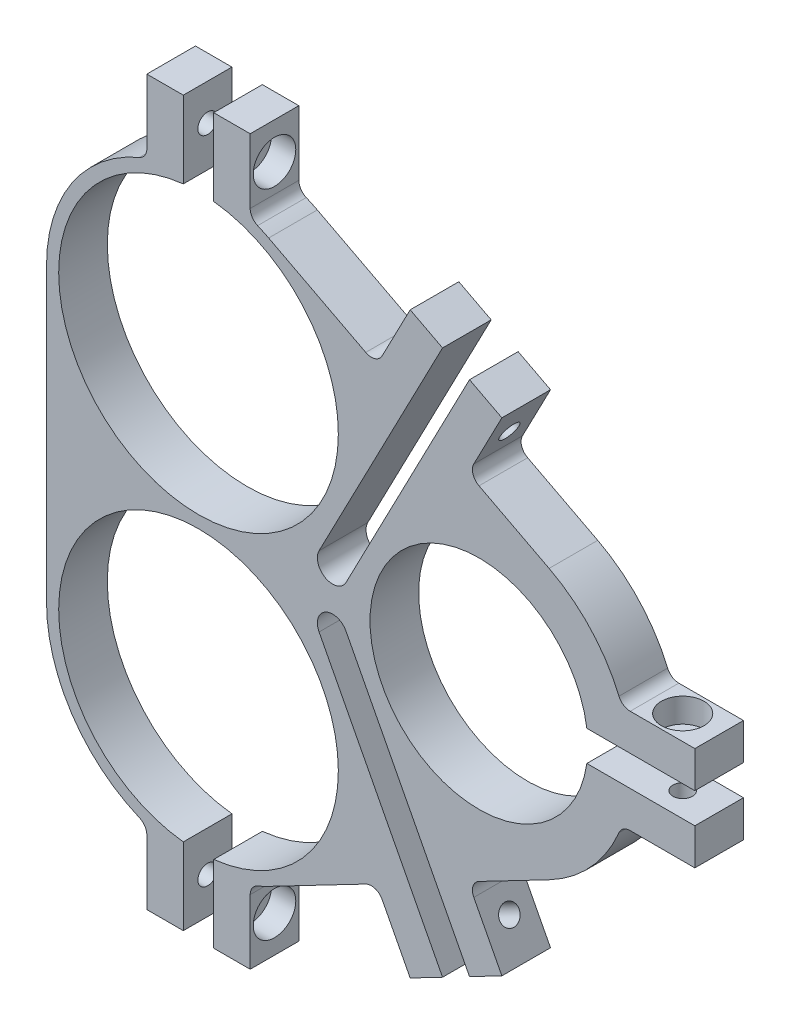
SolidWorks part; units mm, degrees
ref_plane "Front Plane" through (0, 0, 0) normal (0, 0, 1) x (1, 0, 0)
ref_plane "Top Plane" through (0, 0, 0) normal (0, 1, 0) x (1, 0, 0)
ref_plane "Right Plane" through (0, 0, 0) normal (1, 0, 0) x (0, 0, -1)
sketch "Sketch1" plane through (0, 0, 0) normal (0, 0, 1) x (1, 0, 0)
  line L0 (-39.6875, 76.2) -> (-39.6875, 0)
  line L1 (-39.6875, 38.1) -> (73.2318, 38.1) construction
  line L2 (18.3173, 111.4076) -> (46.4834, 96.7537)
  line L3 (3.9688, -36.2962) -> (3.9688, -56.3731)
  line L4 (0, 76.2) -> (0, 0) construction
  line L5 (-13.4938, -37.3231) -> (-13.4938, -56.3731)
  line L6 (3.9688, -56.3731) -> (13.4938, -56.3731)
  line L7 (-3.9688, -56.3731) -> (-13.4938, -56.3731)
  line L8 (13.4938, -37.3231) -> (13.4938, -56.3731)
  line L9 (-3.9687, -36.2962) -> (-3.9688, -56.3731)
  line L10 (18.3173, -35.2076) -> (46.4834, -20.5537)
  line L11 (13.4938, 113.5231) -> (13.4938, 132.5731)
  line L12 (-3.9688, 132.5731) -> (-13.4938, 132.5731)
  line L13 (3.9688, 132.5731) -> (13.4938, 132.5731)
  line L14 (3.9688, 132.5731) -> (3.9688, 112.4962)
  line L15 (-13.4938, 113.5231) -> (-13.4938, 132.5731)
  line L16 (54.9332, 92.3576) -> (61.9747, 88.6941) construction
  line L17 (54.9332, 92.3576) -> (31.487, 47.2919)
  line L18 (-3.9688, 132.5731) -> (-3.9688, 112.4962)
  line L19 (61.9747, 88.6941) -> (38.5286, 43.6284)
  line L20 (31.487, 47.2919) -> (38.5286, 43.6284) construction
  line L21 (54.9332, -16.1576) -> (31.487, 28.9081)
  line L22 (54.9332, 92.3576) -> (63.7255, 109.2572)
  line L23 (3.9688, 132.5731) -> (-3.9688, 132.5731) construction
  line L24 (46.4834, 96.7537) -> (55.2757, 113.6534)
  line L25 (3.9688, -56.3731) -> (-3.9688, -56.3731) construction
  line L26 (63.7255, 109.2572) -> (55.2757, 113.6534)
  line L27 (35.0078, 45.4601) -> (58.454, 90.5259) construction
  line L28 (61.9747, 88.6941) -> (70.767, 105.5938)
  line L29 (70.767, 105.5938) -> (79.2168, 101.1976)
  line L30 (70.4245, 84.298) -> (79.2168, 101.1976)
  line L31 (70.4245, 84.298) -> (91.5491, 73.3076)
  line L32 (61.9747, -12.4941) -> (38.5286, 32.5716)
  line L33 (70.4245, -8.098) -> (79.2168, -24.9976)
  line L34 (70.767, -29.3938) -> (79.2168, -24.9976)
  line L35 (61.9747, -12.4941) -> (70.767, -29.3938)
  line L36 (54.9332, -16.1576) -> (63.7255, -33.0572)
  line L37 (63.7255, -33.0572) -> (55.2757, -37.4534)
  line L38 (46.4834, -20.5537) -> (55.2757, -37.4534)
  line L39 (35.0078, 30.7399) -> (58.454, -14.3259) construction
  line L40 (54.9332, -16.1576) -> (61.9747, -12.4941) construction
  line L41 (70.4245, -8.098) -> (91.5491, 2.8924)
  line L42 (101.4016, 42.0688) -> (129.6049, 42.0688)
  line L43 (129.6049, 42.0688) -> (129.6049, 51.5938)
  line L44 (129.6049, 51.5938) -> (110.5549, 51.5938)
  line L45 (101.4016, 34.1313) -> (129.6049, 34.1313)
  line L46 (129.6049, 34.1313) -> (129.6049, 24.6063)
  line L47 (129.6049, 24.6063) -> (110.5549, 24.6062)
  arc A0 (3.9688, -36.2962) -> (-3.9687, -36.2962) centre (0, 0) ccw
  arc A1 (-3.9688, 112.4962) -> (3.9688, 112.4962) centre (0, 76.2) ccw
  arc A2 (13.4938, 113.5231) -> (18.3173, 111.4076) centre (0, 76.2) cw
  arc A3 (-39.6875, 0) -> (-13.4938, -37.3231) centre (0, 0) ccw
  arc A4 (101.4016, 42.0688) -> (101.4016, 34.1313) centre (73.2318, 38.1) ccw
  arc A5 (13.4938, -37.3231) -> (18.3173, -35.2076) centre (0, 0) ccw
  arc A6 (-39.6875, 76.2) -> (-13.4938, 113.5231) centre (0, 76.2) cw
  arc A7 (110.5549, 51.5938) -> (110.5549, 24.6062) centre (73.2318, 38.1) ccw construction
  circle A8 centre (0, 0) radius 36.5125 construction
  circle A9 centre (0, 76.2) radius 36.5125 construction
  circle A10 centre (0, 0) radius 39.6875 construction
  circle A11 centre (73.2318, 38.1) radius 36.5125 construction
  circle A12 centre (0, 76.2) radius 39.6875 construction
  arc A13 (91.5491, 73.3076) -> (110.5549, 51.5938) centre (73.2318, 38.1) cw
  circle A14 centre (35.0078, 45.4601) radius 3.9687 construction
  arc A15 (31.487, 47.2919) -> (38.5286, 43.6284) centre (35.0078, 45.4601) ccw
  circle A16 centre (35.0078, 30.7399) radius 3.9687 construction
  arc A17 (31.487, 28.9081) -> (38.5286, 32.5716) centre (35.0078, 30.7399) cw
  arc A18 (110.5549, 24.6062) -> (91.5491, 2.8924) centre (73.2318, 38.1) cw
  point P14 (0, 36.5125)
  dimension "D2" = 56.896
  dimension "D4" = 73.025
  dimension "D5" = 73.025
  dimension "D7" = 79.375
  dimension "D9" = 79.375
  dimension "D10" = 73.025
  dimension "D11" = 7.9375
  dimension "D1" = 7.9375
  dimension "D3" = 76.2
  dimension "D6" = 9.525
  dimension "D8" = 19.05
  dimension "D12" = 82.55
  dimension "D13" = 41.275
  dimension "D14" = 50.8
  dimension "D15" = 19.05
  dimension "D16" = 9.525
  dimension "D17" = 9.525
  dimension "D18" = 7.9375
  dimension "D19" = 19.05
extrude "Extrude1" add sketch "Sketch1" along normal mid plane 12.7
hole_wizard "CBORE for 1/4 Socket Head Cap Screw1" positions "Sketch3" profile "Sketch2" counterbore size "1/4" standard "Ansi Inch" end condition up to next
sketch "Sketch3" plane through (13.4938, 0, 0) normal (1, 0, 0) x (0, 0, -1)
  line L0 (6.35, 132.5731) -> (-6.35, 113.5231) construction
  point P0 (0, 123.0481)
sketch "Sketch2" plane through (13.4938, 123.0481, 0) normal (0, 1, 0) x (0, 0, -1)
  line L0 (0, 0) -> (0, 9.525)
  line L1 (0, 9.525) -> (3.3782, 9.525)
  line L3 (3.3782, 9.525) -> (3.3782, 6.35)
  line L4 (3.3782, 6.35) -> (5.5562, 6.35)
  line L5 (5.5562, 6.35) -> (5.5562, 0)
  line L7 (5.5562, 0) -> (0, 0)
  line L11 (0, -6.35) -> (0, 107.95) construction
  dimension "Thru Hole Dia." = 6.7564
  dimension "Thru Hole Depth" = 9.525
  dimension "C'Bore Dia." = 11.1125
  dimension "C'Bore Depth" = 6.35
hole_wizard "1/4-20 Tapped Hole1" positions "Sketch5" profile "Sketch4" tap size "1/4-20" standard "Ansi Inch" end condition through all
sketch "Sketch5" plane through (-3.9687, 0, 0) normal (1, 0, 0) x (0, 0, -1)
  point P0 (0, 123.0481)
sketch "Sketch4" plane through (-3.9688, 123.0481, 0) normal (0, 1, 0) x (0, 0, -1)
  line L0 (0, 0) -> (0, 35.7188)
  line L1 (0, 35.7188) -> (2.5527, 35.7188)
  line L2 (2.5527, 35.7188) -> (2.5527, 0)
  line L5 (2.5527, 0) -> (0, 0)
  line L11 (0, -6.35) -> (0, 107.95) construction
  dimension "Thru Tap Drill Dia." = 5.1054
  dimension "Thru Tap Drill Depth" = 35.7188
cosmetic thread "Hole Thread1" parameters "D2"=6.35
hole_wizard "CBORE for 1/4 Socket Head Cap Screw3" positions "Sketch16" profile "Sketch17" counterbore size "1/4" standard "Ansi Inch" end condition up to next
sketch "Sketch16" plane through (13.4938, 0, 0) normal (1, 0, 0) x (0, 0, -1)
  line L0 (6.35, -37.3231) -> (-6.35, -56.3731) construction
  point P0 (0, -46.8481)
sketch "Sketch17" plane through (13.4938, -46.8481, 0) normal (0, 1, 0) x (0, 0, -1)
  line L0 (0, 0) -> (0, 9.525)
  line L1 (0, 9.525) -> (3.3782, 9.525)
  line L3 (3.3782, 9.525) -> (3.3782, 6.35)
  line L4 (3.3782, 6.35) -> (5.5562, 6.35)
  line L5 (5.5562, 6.35) -> (5.5562, 0)
  line L7 (5.5562, 0) -> (0, 0)
  line L11 (0, -6.35) -> (0, 107.95) construction
  dimension "Thru Hole Dia." = 6.7564
  dimension "Thru Hole Depth" = 9.525
  dimension "C'Bore Dia." = 11.1125
  dimension "C'Bore Depth" = 6.35
hole_wizard "1/4-20 Tapped Hole4" positions "Sketch19" profile "Sketch21" tap size "1/4-20" standard "Ansi Inch" end condition through all
sketch "Sketch19" plane through (-3.9687, 0, 0) normal (1, 0, 0) x (0, 0, -1)
  point P0 (0, -46.8481)
sketch "Sketch21" plane through (-3.9687, -46.8481, 0) normal (0, 1, 0) x (0, 0, -1)
  line L0 (0, 0) -> (0, 35.7188)
  line L1 (0, 35.7188) -> (2.5527, 35.7188)
  line L2 (2.5527, 35.7188) -> (2.5527, 0)
  line L5 (2.5527, 0) -> (0, 0)
  line L11 (0, -6.35) -> (0, 107.95) construction
  dimension "Thru Tap Drill Dia." = 5.1054
  dimension "Thru Tap Drill Depth" = 35.7188
cosmetic thread "Hole Thread4" parameters "D2"=6.35
sketch "Sketch29" plane through (20.9079, -10.8777, 0) normal (0.8871, -0.4615, 0) x (0, 0, -1)
  line L0 (6.35, 126.3361) -> (-6.35, 107.2861) construction
hole_wizard "Tap Drill for 1/4-20 Tap1" positions "Sketch30" profile "Sketch31" hole size "1/4-20" standard "ANSI Inch" end condition up to next
sketch "Sketch30" plane through (20.9079, -10.8777, 0) normal (0.8871, -0.4615, 0) x (0, 0, -1)
  line L0 (6.35, 126.3361) -> (-6.35, 107.2861) construction
  point P0 (0, 116.8111)
sketch "Sketch31" plane through (74.8207, 92.7478, 0) normal (0, 0, 1) x (0.4615, 0.8871, 0)
  line L0 (0, 0) -> (0, 9.525)
  line L1 (0, 9.525) -> (2.5527, 9.525)
  line L2 (2.5527, 9.525) -> (2.5527, 0)
  line L5 (2.5527, 0) -> (0, 0)
  line L11 (0, -6.35) -> (0, 107.95) construction
  dimension "Thru Hole Dia." = 5.1054
  dimension "Thru Hole Depth" = 9.525
sketch "Sketch41" plane through (0, 51.5938, 0) normal (0, 1, 0) x (1, 0, 0)
  line L0 (129.6049, 6.35) -> (110.5549, -6.35) construction
hole_wizard "CBORE for 1/4 Socket Head Cap Screw6" positions "Sketch42" profile "Sketch43" counterbore size "1/4" standard "ANSI Inch" end condition up to next
sketch "Sketch42" plane through (0, 51.5938, 0) normal (0, 1, 0) x (1, 0, 0)
  line L0 (129.6049, 6.35) -> (110.5549, -6.35) construction
  point P0 (120.0799, 0)
sketch "Sketch43" plane through (120.0799, 51.5938, 0) normal (1, 0, 0) x (0, 0, 1)
  line L0 (0, 0) -> (0, 9.525)
  line L1 (0, 9.525) -> (3.3782, 9.525)
  line L3 (3.3782, 9.525) -> (3.3782, 6.35)
  line L4 (3.3782, 6.35) -> (5.5562, 6.35)
  line L5 (5.5562, 6.35) -> (5.5563, 0)
  line L7 (5.5563, 0) -> (0, 0)
  line L11 (0, -6.35) -> (0, 107.95) construction
  dimension "Thru Hole Dia." = 6.7564
  dimension "Thru Hole Depth" = 9.525
  dimension "C'Bore Dia." = 11.1125
  dimension "C'Bore Depth" = 6.35
hole_wizard "1/4-20 Tapped Hole7" positions "Sketch44" profile "Sketch45" tap size "1/4-20" standard "ANSI Inch" end condition up to next
sketch "Sketch44" plane through (0, 34.1313, 0) normal (0, 1, 0) x (1, 0, 0)
  line L0 (129.6049, 6.35) -> (110.5549, -6.35) construction
  point P0 (120.0799, 0)
sketch "Sketch45" plane through (120.0799, 34.1313, 0) normal (1, 0, 0) x (0, 0, 1)
  line L0 (0, 0) -> (0, 9.525)
  line L1 (0, 9.525) -> (2.5527, 9.525)
  line L2 (2.5527, 9.525) -> (2.5527, 0)
  line L5 (2.5527, 0) -> (0, 0)
  line L11 (0, -6.35) -> (0, 107.95) construction
  dimension "Thru Tap Drill Dia." = 5.1054
  dimension "Thru Tap Drill Depth" = 9.525
cosmetic thread "Hole Thread7" parameters "D2"=6.35
sketch "Sketch46" plane through (52.1072, 27.1096, 0) normal (0.8871, 0.4615, 0) x (0, 0, -1)
  line L0 (-6.35, -39.6875) -> (6.35, -58.7375) construction
hole_wizard "Tap Drill for 1/4-20 Tap2" positions "Sketch47" profile "Sketch48" hole size "1/4-20" standard "ANSI Inch" end condition up to next
sketch "Sketch47" plane through (52.1072, 27.1096, 0) normal (0.8871, 0.4615, 0) x (0, 0, -1)
  line L0 (-6.35, -39.6875) -> (6.35, -58.7375) construction
  point P0 (0, -49.2125)
sketch "Sketch48" plane through (74.8207, -16.5478, 0) normal (0, 0, 1) x (-0.4615, 0.8871, 0)
  line L0 (0, 0) -> (0, 9.525)
  line L1 (0, 9.525) -> (2.5527, 9.525)
  line L2 (2.5527, 9.525) -> (2.5527, 0)
  line L5 (2.5527, 0) -> (0, 0)
  line L11 (0, -6.35) -> (0, 107.95) construction
  dimension "Thru Hole Dia." = 5.1054
  dimension "Thru Hole Depth" = 9.525
fillet "Fillet1" radius 3.175 10 edges at (13.4938, 113.5231, 0) (-13.4938, 113.5231, 0) (-13.4938, -37.3231, 0) (13.4938, -37.3231, 0) (46.4834, 96.7537, 0) (70.4245, 84.298, 0) (110.5549, 24.6063, 0) (110.5549, 51.5938, 0) (46.4834, -20.5537, 0) (70.4245, -8.098, 0)
